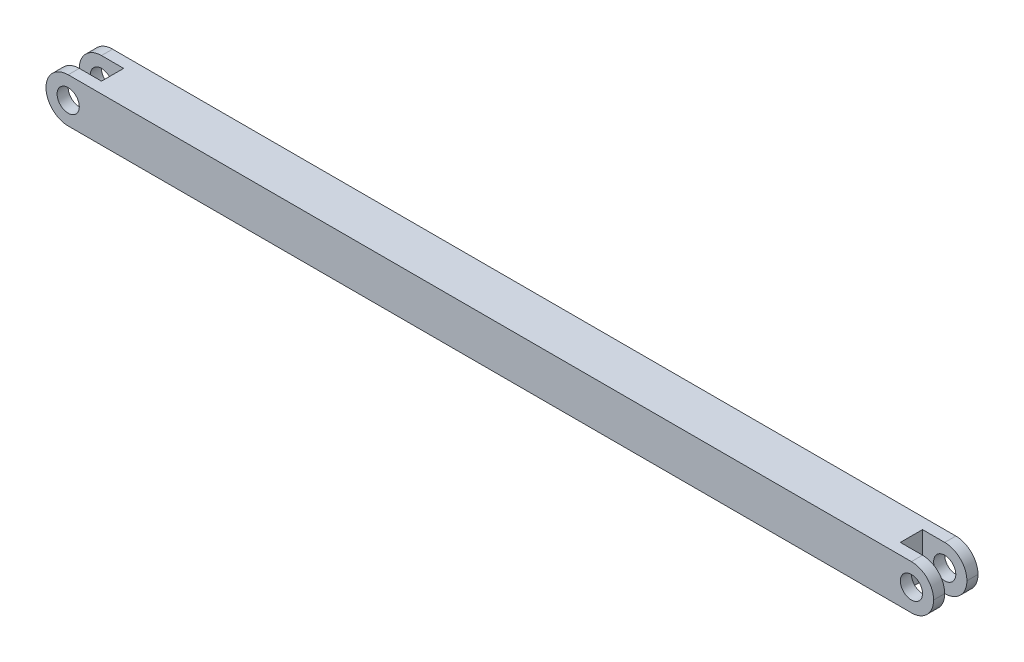
SolidWorks part; units mm, degrees
ref_plane "Front Plane" through (0, 0, 0) normal (0, 0, 1) x (1, 0, 0)
ref_plane "Top Plane" through (0, 0, 0) normal (0, 1, 0) x (1, 0, 0)
ref_plane "Right Plane" through (0, 0, 0) normal (1, 0, 0) x (0, 0, -1)
sketch "Sketch1" plane through (0, 0, 0) normal (0, 0, 1) x (1, 0, 0)
  line L1 (-100, 5) -> (100, 5)
  line L2 (-100, 5) -> (-100, -5)
  line L3 (-100, -5) -> (100, -5)
  line L4 (100, 5) -> (100, -5)
  line L5 (-100, 5) -> (100, -5) construction
  line L6 (-100, -5) -> (100, 5) construction
  point P0 (0, 0)
  dimension "D1" = 200
  dimension "D2" = 10
extrude "Boss-Extrude1" add sketch "Sketch1" along normal blind 10
fillet "Fillet1" radius 5 4 edges at (-100, -5, 5) (-100, 5, 5) (100, -5, 5) (100, 5, 5)
sketch "Sketch2" plane through (0, 0, 10) normal (0, 0, 1) x (1, 0, 0)
  circle A0 centre (95, 0) radius 2.5
  arc A1 (100, 0) -> (95, 5) centre (95, 0) ccw construction
  circle A2 centre (-95, 0) radius 2.5
  arc A3 (-95, 5) -> (-100, 0) centre (-95, 0) ccw construction
  dimension "D1" = 5
  dimension "D2" = 5
extrude "Cut-Extrude1" cut sketch "Sketch2" against normal blind 10
sketch "Sketch3" plane through (0, 5, 0) normal (0, 1, 0) x (1, 0, 0)
  line L0 (-100, -10) -> (-100, 0) construction
  line L1 (-100, -2.5) -> (-90, -2.5)
  line L2 (-100, -2.5) -> (-100, -7.5)
  line L3 (-100, -7.5) -> (-90, -7.5)
  line L4 (-90, -2.5) -> (-90, -7.5)
  line L5 (95, 0) -> (-95, 0) construction
  line L6 (0, 0) -> (0, -10) construction
  line L7 (95, -10) -> (-95, -10) construction
  line L8 (90, -2.5) -> (90, -7.5)
  line L9 (100, -7.5) -> (90, -7.5)
  line L10 (100, -2.5) -> (100, -7.5)
  line L11 (100, -2.5) -> (90, -2.5)
  dimension "D1" = 5
  dimension "D2" = 10
  dimension "D3" = 2.5
extrude "Cut-Extrude2" cut sketch "Sketch3" against normal blind 10
